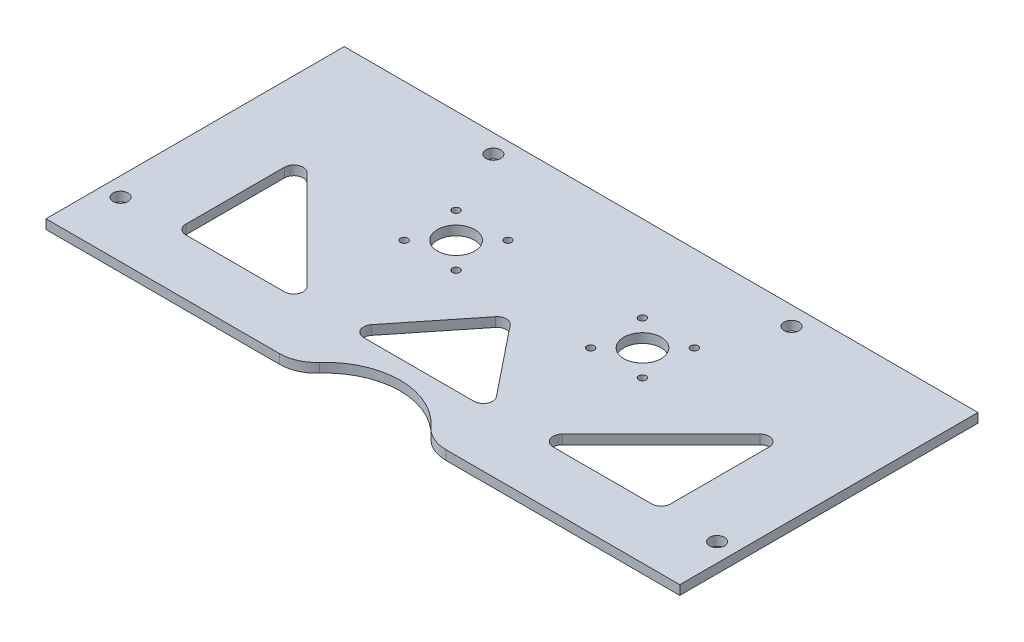
SolidWorks part; units mm, degrees
material "6061-T6 (SS)"
ref_plane "Front Plane" through (0, 0, 0) normal (0, 0, 1) x (1, 0, 0)
ref_plane "Top Plane" through (0, 0, 0) normal (0, 1, 0) x (1, 0, 0)
ref_plane "Right Plane" through (0, 0, 0) normal (1, 0, 0) x (0, 0, -1)
sketch "Sketch1" plane through (0, 0, 0) normal (0, 1, 0) x (1, 0, 0)
  line L0 (0, 101.6) -> (0, 0)
  line L1 (0, 0) -> (215.9, 0)
  line L2 (0, 0) -> (0, 228.6)
  line L3 (0, 228.6) -> (215.9, 228.6)
  line L4 (215.9, 0) -> (215.9, 228.6)
  line L5 (0, 127) -> (85.953, 127)
  line L6 (0, 127) -> (0, 101.6)
  line L7 (0, 101.6) -> (85.953, 101.6)
  line L8 (85.953, 127) -> (85.953, 101.6)
  line L9 (215.9, 127) -> (129.947, 127)
  line L10 (215.9, 127) -> (215.9, 101.6)
  line L11 (215.9, 101.6) -> (129.947, 101.6)
  line L12 (129.947, 127) -> (129.947, 101.6)
  line L13 (215.9, 0) -> (215.9, 101.6)
  circle A0 centre (107.95, 114.3) radius 25.4
  point P13 (85.953, 114.3)
  point P18 (0, 114.3)
  dimension "D4" = 50.8
  dimension "D5" = 85.953
  dimension "D1" = 228.6
  dimension "D2" = 215.9
  dimension "D3" = 25.4
extrude "Boss-Extrude1" add sketch "Sketch1" along normal blind 3.175 contours A0 L9 L4 L3 L2 L5 region at (107.95, 0, -178.6387)
sketch "Sketch2" plane through (0, 3.175, 0) normal (0, 1, 0) x (1, 0, 0)
  line L0 (0, 190.5) -> (76.2, 190.5) construction
  line L2 (76.2, 190.5) -> (139.7, 190.5) construction
  line L3 (0, 228.6) -> (215.9, 228.6) construction
  line L4 (215.9, 127) -> (215.9, 228.6) construction
  line L5 (139.7, 190.5) -> (215.9, 190.5) construction
  line L8 (0, 127) -> (0, 228.6) construction
  circle A0 centre (76.2, 190.5) radius 6.35
  circle A1 centre (139.7, 190.5) radius 6.35
  dimension "D1" = 12.7
  dimension "D2" = 38.1
  dimension "D3" = 63.5
extrude "Cut-Extrude1" cut sketch "Sketch2" against normal through all
fillet "Fillet1" radius 12.7 2 edges at (129.947, 1.5875, -127) (85.953, 1.5875, -127)
sketch "Sketch3" plane through (0, 3.175, 0) normal (0, 1, 0) x (1, 0, 0)
  line L1 (67.3612, 181.6612) -> (85.0388, 181.6612) construction
  line L2 (67.3612, 181.6612) -> (67.3612, 199.3388) construction
  line L3 (67.3612, 199.3388) -> (85.0388, 199.3388) construction
  line L4 (85.0388, 181.6612) -> (85.0388, 199.3388) construction
  line L5 (67.3612, 181.6612) -> (85.0388, 199.3388) construction
  line L6 (67.3612, 199.3388) -> (85.0388, 181.6612) construction
  line L7 (130.8612, 181.6612) -> (148.5388, 181.6612) construction
  line L8 (130.8612, 181.6612) -> (130.8612, 199.3388) construction
  line L9 (130.8612, 199.3388) -> (148.5388, 199.3388) construction
  line L10 (148.5388, 181.6612) -> (148.5388, 199.3388) construction
  line L11 (130.8612, 181.6612) -> (148.5388, 199.3388) construction
  line L12 (130.8612, 199.3388) -> (148.5388, 181.6612) construction
  circle A0 centre (85.0388, 199.3388) radius 1.27
  circle A1 centre (67.3612, 181.6612) radius 1.27
  circle A2 centre (67.3612, 199.3388) radius 1.27
  circle A3 centre (85.0388, 181.6612) radius 1.27
  circle A4 centre (130.8612, 181.6612) radius 1.27
  circle A5 centre (148.5388, 181.6612) radius 1.27
  circle A6 centre (148.5388, 199.3388) radius 1.27
  circle A7 centre (130.8612, 199.3388) radius 1.27
  point P0 (76.2, 190.5)
  point P6 (139.7, 190.5)
  dimension "D2" = 2.54
  dimension "D1" = 25
extrude "Cut-Extrude2" cut sketch "Sketch3" against normal through all
sketch "Sketch4" plane through (0, 3.175, 0) normal (0, 1, 0) x (1, 0, 0)
  line L0 (0, 127) -> (0, 228.6) construction
  line L1 (0, 127) -> (79.5519, 127) construction
  line L2 (215.9, 127) -> (136.3481, 127) construction
  line L3 (215.9, 127) -> (215.9, 228.6) construction
  line L4 (0, 228.6) -> (215.9, 228.6) construction
  circle A0 centre (6.35, 146.05) radius 2.54
  circle A1 centre (57.15, 222.25) radius 2.54
  circle A2 centre (158.75, 222.25) radius 2.54
  circle A3 centre (209.55, 146.05) radius 2.54
  dimension "D1" = 5.08
  dimension "D2" = 6.35
  dimension "D3" = 19.05
  dimension "D4" = 19.05
  dimension "D5" = 6.35
  dimension "D6" = 57.15
  dimension "D7" = 6.35
  dimension "D8" = 6.35
  dimension "D9" = 57.15
extrude "Cut-Extrude3" cut sketch "Sketch4" against normal through all
sketch "Sketch5" plane through (0, 3.175, 0) normal (0, 1, 0) x (1, 0, 0)
  line L0 (25.4, 190.5) -> (25.4, 146.05)
  line L1 (25.4, 146.05) -> (69.85, 146.05)
  line L2 (69.85, 146.05) -> (25.4, 190.5)
  line L3 (107.95, 139.7) -> (107.95, 228.6) construction
  line L4 (0, 228.6) -> (215.9, 228.6) construction
  line L5 (0, 127) -> (0, 228.6) construction
  line L6 (0, 127) -> (79.5519, 127) construction
  line L7 (190.5, 146.05) -> (146.05, 146.05)
  line L8 (190.5, 190.5) -> (190.5, 146.05)
  line L9 (146.05, 146.05) -> (190.5, 190.5)
  arc A0 (126.882, 131.2333) -> (89.018, 131.2333) centre (107.95, 114.3) ccw construction
  dimension "D1" = 25.4
  dimension "D2" = 38.1
  dimension "D3" = 38.1
  dimension "D4" = 19.05
extrude "Cut-Extrude4" cut sketch "Sketch5" against normal through all
sketch "Sketch6" plane through (0, 3.175, 0) normal (0, 1, 0) x (1, 0, 0)
  line L0 (82.55, 146.05) -> (133.35, 146.05)
  line L1 (133.35, 146.05) -> (107.95, 177.8)
  line L2 (107.95, 177.8) -> (82.55, 146.05)
  arc A0 (126.882, 131.2333) -> (89.018, 131.2333) centre (107.95, 114.3) ccw construction
  point P3 (107.95, 146.05)
  point P8 (107.95, 139.7)
  dimension "D1" = 6.35
  dimension "D2" = 50.8
  dimension "D3" = 31.75
extrude "Cut-Extrude5" cut sketch "Sketch6" against normal through all
fillet "Fillet2" radius 3.175 9 edges at (69.85, 1.5875, -146.05) (25.4, 1.5875, -146.05) (146.05, 1.5875, -146.05) (190.5, 1.5875, -146.05) (190.5, 1.5875, -190.5) (25.4, 1.5875, -190.5) (133.35, 1.5875, -146.05) (82.55, 1.5875, -146.05) (107.95, 1.5875, -177.8)
